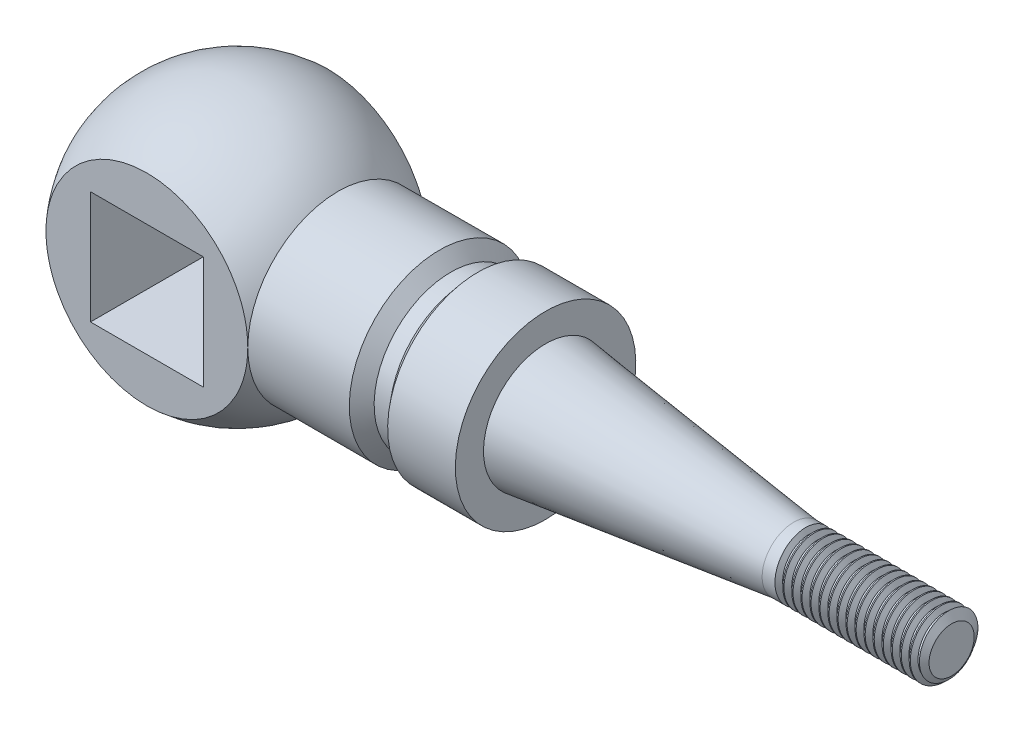
SolidWorks part; units mm, degrees
material "AISI 1020"
ref_plane "Front" through (0, 0, 0) normal (0, 0, 1) x (1, 0, 0)
ref_plane "Top" through (0, 0, 0) normal (0, 1, 0) x (1, 0, 0)
ref_plane "Right" through (0, 0, 0) normal (1, 0, 0) x (0, 0, -1)
sketch "Sketch1" plane through (0, 0, 0) normal (0, 0, 1) x (1, 0, 0)
  line L0 (-100.559, 0) -> (100.559, 0)
  line L1 (-72.161, 25.4) -> (-43.586, 25.4)
  line L2 (-43.586, 25.4) -> (-40.411, 21.59)
  line L3 (-40.411, 21.59) -> (-35.966, 21.59)
  line L4 (-35.966, 21.59) -> (-32.791, 25.4)
  line L5 (-32.791, 25.4) -> (-13.741, 25.4)
  line L6 (-13.741, 25.4) -> (-13.741, 17.4665)
  line L7 (-13.741, 17.4665) -> (56.109, 8.89)
  line L8 (56.109, 8.89) -> (100.559, 8.89)
  line L9 (100.559, 8.89) -> (100.559, 0)
  line L10 (-100.559, 0) -> (-138.659, 0)
  arc A1 (-72.161, 25.4) -> (-138.659, 0) centre (-100.559, 0) ccw
  point P4 (0, 0)
  dimension "D2" = 76.2
  dimension "D3" = 3.175
  dimension "D4" = 3.175
  dimension "D5" = 4.445
  dimension "D6" = 19.05
  dimension "D7" = 69.85
  dimension "D8" = 7
  dimension "D9" = 44.45
  dimension "D10" = 8.89
  dimension "D11" = 28.575
  dimension "D12" = 25.4
  dimension "D13" = 21.59
revolve "Revolve1" add sketch "Sketch1" angle 360 about L0
ref_plane "Plane1" through (0, 38.1, 0) normal (0, 1, 0) x (1, 0, 0)
sketch "Sketch2" plane through (0, 38.1, 0) normal (0, 1, 0) x (1, 0, 0)
  line L0 (0, 0) -> (-200.6051, 0) construction
  line L1 (-146.5672, -46.7129) -> (-65.9939, -46.7129)
  line L2 (-146.5672, -46.7129) -> (-146.5672, -25.4)
  line L3 (-146.5672, -25.4) -> (-65.9939, -25.4)
  line L4 (-65.9939, -46.7129) -> (-65.9939, -25.4)
  line L5 (-150.9858, 50.8) -> (-49.6193, 50.8)
  line L6 (-150.9858, 50.8) -> (-150.9858, 25.4)
  line L7 (-150.9858, 25.4) -> (-49.6193, 25.4)
  line L8 (-49.6193, 50.8) -> (-49.6193, 25.4)
  line L9 (-100.3026, 25.4) -> (-100.3026, -25.4) construction
  point P13 (-100.3026, 0)
  dimension "D1" = 50.8
  dimension "D2" = 25.4
extrude "Cut-Extrude1" cut sketch "Sketch2" against normal through all
thread "Thread1" pitch 2.54 start angle 0, offset 2.032, length 40.132, pitch 2.54, diameter 17.78
ref_plane "Plane2" through (102.591, 0, 8.89) normal (0, -1, 0) x (0, 0, 1)
sketch "Thread Profile1" plane through (102.591, 0, 8.89) normal (0, -1, 0) x (0, 0, 1)
  line L0 (0, 0) -> (0, 2.54) construction
  line L11 (0, 0) -> (0, 2.2225)
  line L12 (0, 2.2225) -> (-1.3748, 1.4287)
  line L13 (-1.3748, 1.4287) -> (-1.3748, 0.7937)
  line L15 (-1.3748, 0.7937) -> (0, 0)
  line L17 (-1.3748, 1.1112) -> (0, 1.1112) construction
  point P2 (0, 0)
  dimension "Pitch" = 2.54
  dimension "Profile_Angle" = 60
  dimension "Profile_Land" = 0.635
  dimension "Profile_Height" = 1.3748
sketch "Sketch9" plane through (0, 0, 0) normal (0, 1, 0) x (1, 0, 0)
  line L0 (100.559, 0) -> (102.7621, 0) construction
  line L1 (100.559, -2.7472) -> (100.559, 7.601) construction
  line L2 (100.559, -6.35) -> (103.3334, -6.35)
  line L3 (103.3334, -6.35) -> (103.3334, -10.1891)
  line L4 (103.3334, -10.1891) -> (98.3425, -10.1891)
  line L5 (98.3425, -10.1891) -> (100.559, -6.35)
  line L6 (100.559, -8.89) -> (100.559, -2.7472) construction
  dimension "D1" = 6.35
  dimension "D2" = 30
revolve "Cut-Revolve2" cut sketch "Sketch9" angle 360 about L0
sketch "Sketch10" plane through (0, 0, 25.4) normal (0, 0, 1) x (1, 0, 0)
  line L1 (-116.434, 15.875) -> (-84.684, 15.875)
  line L2 (-116.434, 15.875) -> (-116.434, -15.875)
  line L3 (-116.434, -15.875) -> (-84.684, -15.875)
  line L4 (-84.684, 15.875) -> (-84.684, -15.875)
  line L5 (-116.434, 15.875) -> (-84.684, -15.875) construction
  line L6 (-116.434, -15.875) -> (-84.684, 15.875) construction
  circle A0 centre (-100.559, 0) radius 28.3981 construction
  point P0 (-100.559, 0)
  dimension "D1" = 31.75
extrude "Cut-Extrude2" cut sketch "Sketch10" against normal through all
